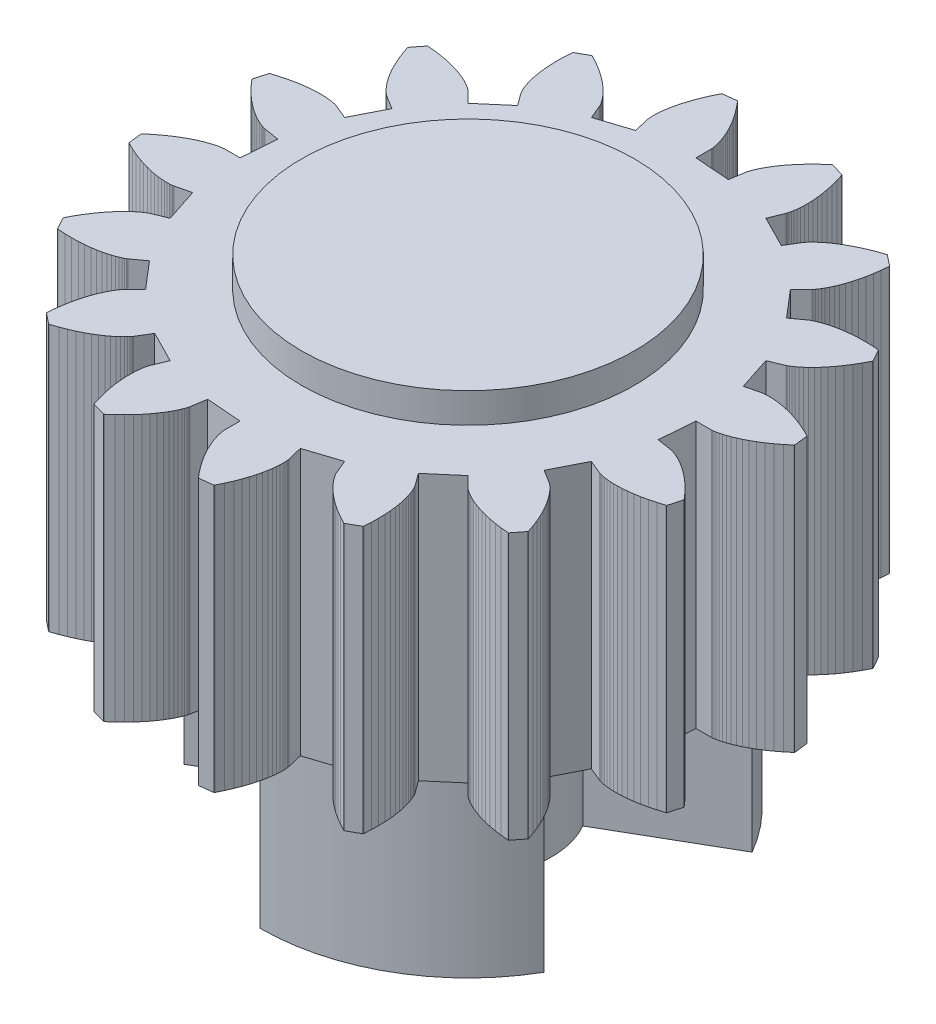
SolidWorks part; units mm, degrees
ref_plane "Front Plane" through (0, 0, 0) normal (0, 0, 1) x (1, 0, 0)
ref_plane "Top Plane" through (0, 0, 0) normal (0, 1, 0) x (1, 0, 0)
ref_plane "Right Plane" through (0, 0, 0) normal (1, 0, 0) x (0, 0, -1)
sketch "Sketch1" plane through (0, 0, 0) normal (0, 1, 0) x (1, 0, 0)
  line L0 (6.85, 0) -> (7.3095, 0)
  line L1 (7.3095, 0) -> (7.322, 0.0006)
  line L2 (7.322, 0.0006) -> (7.3483, 0.0028)
  line L3 (7.3483, 0.0028) -> (7.3883, 0.0079)
  line L4 (7.3883, 0.0079) -> (7.4418, 0.0172)
  line L5 (7.4418, 0.0172) -> (7.5084, 0.0317)
  line L6 (7.5084, 0.0317) -> (7.5878, 0.0526)
  line L7 (7.5878, 0.0526) -> (7.6795, 0.0812)
  line L8 (7.6795, 0.0812) -> (7.7829, 0.1183)
  line L9 (7.7829, 0.1183) -> (7.8975, 0.1653)
  line L10 (7.8975, 0.1653) -> (8.0225, 0.223)
  line L11 (8.0225, 0.223) -> (8.1573, 0.2925)
  line L12 (8.1573, 0.2925) -> (8.3011, 0.3747)
  line L13 (8.3011, 0.3747) -> (8.4528, 0.4705)
  line L14 (8.4528, 0.4705) -> (8.6117, 0.5808)
  line L15 (8.6117, 0.5808) -> (8.7767, 0.7063)
  line L16 (8.7767, 0.7063) -> (8.9467, 0.8478)
  line L17 (8.9467, 0.8478) -> (8.9575, 0.8572)
  line L18 (8.9575, 0.8572) -> (8.9588, 0.8583)
  line L19 (8.9588, 0.8583) -> (8.9589, 0.8586)
  line L20 (8.9589, 0.8586) -> (8.9086, 1.2795)
  line L21 (8.9086, 1.2795) -> (8.9084, 1.2798)
  line L22 (8.9084, 1.2798) -> (8.9068, 1.2806)
  line L23 (8.9068, 1.2806) -> (8.8941, 1.2872)
  line L24 (8.8941, 1.2872) -> (8.6955, 1.3845)
  line L25 (8.6955, 1.3845) -> (8.5056, 1.4676)
  line L26 (8.5056, 1.4676) -> (8.3252, 1.5373)
  line L27 (8.3252, 1.5373) -> (8.1551, 1.5946)
  line L28 (8.1551, 1.5946) -> (7.996, 1.6405)
  line L29 (7.996, 1.6405) -> (7.8486, 1.6762)
  line L30 (7.8486, 1.6762) -> (7.7135, 1.7028)
  line L31 (7.7135, 1.7028) -> (7.5911, 1.7214)
  line L32 (7.5911, 1.7214) -> (7.4818, 1.7331)
  line L33 (7.4818, 1.7331) -> (7.386, 1.7392)
  line L34 (7.386, 1.7392) -> (7.3039, 1.7408)
  line L35 (7.3039, 1.7408) -> (7.2357, 1.7392)
  line L36 (7.2357, 1.7392) -> (7.1816, 1.7356)
  line L37 (7.1816, 1.7356) -> (7.1415, 1.7311)
  line L38 (7.1415, 1.7311) -> (7.1154, 1.7271)
  line L39 (7.1154, 1.7271) -> (7.1031, 1.7247)
  line L40 (7.1031, 1.7247) -> (6.6566, 1.6163)
  line L41 (6.6566, 1.6163) -> (6.3286, 2.6214)
  line L42 (6.3286, 2.6214) -> (6.7531, 2.7972)
  line L43 (6.7531, 2.7972) -> (6.7644, 2.8025)
  line L44 (6.7644, 2.8025) -> (6.7879, 2.8147)
  line L45 (6.7879, 2.8147) -> (6.8229, 2.8347)
  line L46 (6.8229, 2.8347) -> (6.8688, 2.8637)
  line L47 (6.8688, 2.8637) -> (6.9248, 2.9026)
  line L48 (6.9248, 2.9026) -> (6.9901, 2.9524)
  line L49 (6.9901, 2.9524) -> (7.0638, 3.0138)
  line L50 (7.0638, 3.0138) -> (7.1452, 3.0877)
  line L51 (7.1452, 3.0877) -> (7.2331, 3.1749)
  line L52 (7.2331, 3.1749) -> (7.3265, 3.2761)
  line L53 (7.3265, 3.2761) -> (7.4245, 3.3919)
  line L54 (7.4245, 3.3919) -> (7.5258, 3.5228)
  line L55 (7.5258, 3.5228) -> (7.6293, 3.6694)
  line L56 (7.6293, 3.6694) -> (7.7339, 3.8321)
  line L57 (7.7339, 3.8321) -> (7.8383, 4.0112)
  line L58 (7.8383, 4.0112) -> (7.9413, 4.207)
  line L59 (7.9413, 4.207) -> (7.9476, 4.2198)
  line L60 (7.9476, 4.2198) -> (7.9484, 4.2214)
  line L61 (7.9484, 4.2214) -> (7.9484, 4.2217)
  line L62 (7.9484, 4.2217) -> (7.7408, 4.5913)
  line L63 (7.7408, 4.5913) -> (7.7406, 4.5914)
  line L64 (7.7406, 4.5914) -> (7.7388, 4.5916)
  line L65 (7.7388, 4.5916) -> (7.7245, 4.5928)
  line L66 (7.7245, 4.5928) -> (7.5038, 4.6068)
  line L67 (7.5038, 4.6068) -> (7.2965, 4.6108)
  line L68 (7.2965, 4.6108) -> (7.1032, 4.6062)
  line L69 (7.1032, 4.6062) -> (6.9241, 4.594)
  line L70 (6.9241, 4.594) -> (6.7596, 4.5756)
  line L71 (6.7596, 4.5756) -> (6.6097, 4.5522)
  line L72 (6.6097, 4.5522) -> (6.4747, 4.525)
  line L73 (6.4747, 4.525) -> (6.3545, 4.4953)
  line L74 (6.3545, 4.4953) -> (6.249, 4.4644)
  line L75 (6.249, 4.4644) -> (6.1582, 4.4333)
  line L76 (6.1582, 4.4333) -> (6.0817, 4.4034)
  line L77 (6.0817, 4.4034) -> (6.0194, 4.3758)
  line L78 (6.0194, 4.3758) -> (5.9708, 4.3518)
  line L79 (5.9708, 4.3518) -> (5.9354, 4.3323)
  line L80 (5.9354, 4.3323) -> (5.9128, 4.3186)
  line L81 (5.9128, 4.3186) -> (5.9024, 4.3116)
  line L82 (5.9024, 4.3116) -> (5.5314, 4.0406)
  line L83 (5.5314, 4.0406) -> (4.8437, 4.8437)
  line L84 (4.8437, 4.8437) -> (5.1686, 5.1686)
  line L85 (5.1686, 5.1686) -> (5.177, 5.1778)
  line L86 (5.177, 5.1778) -> (5.1941, 5.198)
  line L87 (5.1941, 5.198) -> (5.2187, 5.23)
  line L88 (5.2187, 5.23) -> (5.25, 5.2743)
  line L89 (5.25, 5.2743) -> (5.2869, 5.3317)
  line L90 (5.2869, 5.3317) -> (5.3282, 5.4026)
  line L91 (5.3282, 5.4026) -> (5.3728, 5.4876)
  line L92 (5.3728, 5.4876) -> (5.4197, 5.587)
  line L93 (5.4197, 5.587) -> (5.4675, 5.7012)
  line L94 (5.4675, 5.7012) -> (5.5151, 5.8305)
  line L95 (5.5151, 5.8305) -> (5.5613, 5.9749)
  line L96 (5.5613, 5.9749) -> (5.6048, 6.1347)
  line L97 (5.6048, 6.1347) -> (5.6444, 6.3097)
  line L98 (5.6444, 6.3097) -> (5.6787, 6.5)
  line L99 (5.6787, 6.5) -> (5.7066, 6.7055)
  line L100 (5.7066, 6.7055) -> (5.7268, 6.9258)
  line L101 (5.7268, 6.9258) -> (5.7278, 6.94)
  line L102 (5.7278, 6.94) -> (5.7279, 6.9418)
  line L103 (5.7279, 6.9418) -> (5.7278, 6.9421)
  line L104 (5.7278, 6.9421) -> (5.3946, 7.2041)
  line L105 (5.3946, 7.2041) -> (5.3943, 7.2041)
  line L106 (5.3943, 7.2041) -> (5.3926, 7.2036)
  line L107 (5.3926, 7.2036) -> (5.3789, 7.1993)
  line L108 (5.3789, 7.1993) -> (5.1696, 7.1277)
  line L109 (5.1696, 7.1277) -> (4.9766, 7.0521)
  line L110 (4.9766, 7.0521) -> (4.7998, 6.9738)
  line L111 (4.7998, 6.9738) -> (4.639, 6.894)
  line L112 (4.639, 6.894) -> (4.494, 6.8141)
  line L113 (4.494, 6.8141) -> (4.3645, 6.7351)
  line L114 (4.3645, 6.7351) -> (4.2502, 6.6583)
  line L115 (4.2502, 6.6583) -> (4.1505, 6.5849)
  line L116 (4.1505, 6.5849) -> (4.0649, 6.5159)
  line L117 (4.0649, 6.5159) -> (3.9929, 6.4525)
  line L118 (3.9929, 6.4525) -> (3.9337, 6.3956)
  line L119 (3.9337, 6.3956) -> (3.8866, 6.3463)
  line L120 (3.8866, 6.3463) -> (3.8509, 6.3054)
  line L121 (3.8509, 6.3054) -> (3.8257, 6.2739)
  line L122 (3.8257, 6.2739) -> (3.8101, 6.2526)
  line L123 (3.8101, 6.2526) -> (3.8031, 6.2422)
  line L124 (3.8031, 6.2422) -> (3.564, 5.8498)
  line L125 (3.564, 5.8498) -> (2.6214, 6.3286)
  line L126 (2.6214, 6.3286) -> (2.7972, 6.7531)
  line L127 (2.7972, 6.7531) -> (2.8015, 6.7648)
  line L128 (2.8015, 6.7648) -> (2.8095, 6.79)
  line L129 (2.8095, 6.79) -> (2.8201, 6.829)
  line L130 (2.8201, 6.829) -> (2.832, 6.8819)
  line L131 (2.832, 6.8819) -> (2.8441, 6.949)
  line L132 (2.8441, 6.949) -> (2.8551, 7.0304)
  line L133 (2.8551, 7.0304) -> (2.8638, 7.126)
  line L134 (2.8638, 7.126) -> (2.869, 7.2357)
  line L135 (2.869, 7.2357) -> (2.8695, 7.3596)
  line L136 (2.8695, 7.3596) -> (2.8641, 7.4972)
  line L137 (2.8641, 7.4972) -> (2.8515, 7.6483)
  line L138 (2.8515, 7.6483) -> (2.8305, 7.8126)
  line L139 (2.8305, 7.8126) -> (2.8001, 7.9894)
  line L140 (2.8001, 7.9894) -> (2.759, 8.1784)
  line L141 (2.759, 8.1784) -> (2.7062, 8.3789)
  line L142 (2.7062, 8.3789) -> (2.6405, 8.5901)
  line L143 (2.6405, 8.5901) -> (2.636, 8.6037)
  line L144 (2.636, 8.6037) -> (2.6354, 8.6054)
  line L145 (2.6354, 8.6054) -> (2.6352, 8.6056)
  line L146 (2.6352, 8.6056) -> (2.227, 8.7201)
  line L147 (2.227, 8.7201) -> (2.2268, 8.72)
  line L148 (2.2268, 8.72) -> (2.2254, 8.7189)
  line L149 (2.2254, 8.7189) -> (2.2144, 8.7097)
  line L150 (2.2144, 8.7097) -> (2.0485, 8.5634)
  line L151 (2.0485, 8.5634) -> (1.8991, 8.4197)
  line L152 (1.8991, 8.4197) -> (1.7657, 8.2797)
  line L153 (1.7657, 8.2797) -> (1.6476, 8.1445)
  line L154 (1.6476, 8.1445) -> (1.5443, 8.0152)
  line L155 (1.5443, 8.0152) -> (1.4549, 7.8927)
  line L156 (1.4549, 7.8927) -> (1.3786, 7.778)
  line L157 (1.3786, 7.778) -> (1.3146, 7.672)
  line L158 (1.3146, 7.672) -> (1.262, 7.5755)
  line L159 (1.262, 7.5755) -> (1.2197, 7.4893)
  line L160 (1.2197, 7.4893) -> (1.1868, 7.4141)
  line L161 (1.1868, 7.4141) -> (1.1622, 7.3505)
  line L162 (1.1622, 7.3505) -> (1.1448, 7.2991)
  line L163 (1.1448, 7.2991) -> (1.1336, 7.2604)
  line L164 (1.1336, 7.2604) -> (1.1273, 7.2347)
  line L165 (1.1273, 7.2347) -> (1.1248, 7.2224)
  line L166 (1.1248, 7.2224) -> (1.0541, 6.7684)
  line L167 (1.0541, 6.7684) -> (0, 6.85)
  line L168 (0, 6.85) -> (0, 7.3095)
  line L169 (0, 7.3095) -> (-0.0006, 7.322)
  line L170 (-0.0006, 7.322) -> (-0.0028, 7.3483)
  line L171 (-0.0028, 7.3483) -> (-0.0079, 7.3883)
  line L172 (-0.0079, 7.3883) -> (-0.0172, 7.4418)
  line L173 (-0.0172, 7.4418) -> (-0.0317, 7.5084)
  line L174 (-0.0317, 7.5084) -> (-0.0526, 7.5878)
  line L175 (-0.0526, 7.5878) -> (-0.0812, 7.6795)
  line L176 (-0.0812, 7.6795) -> (-0.1183, 7.7829)
  line L177 (-0.1183, 7.7829) -> (-0.1653, 7.8975)
  line L178 (-0.1653, 7.8975) -> (-0.223, 8.0225)
  line L179 (-0.223, 8.0225) -> (-0.2925, 8.1573)
  line L180 (-0.2925, 8.1573) -> (-0.3747, 8.3011)
  line L181 (-0.3747, 8.3011) -> (-0.4705, 8.4528)
  line L182 (-0.4705, 8.4528) -> (-0.5808, 8.6117)
  line L183 (-0.5808, 8.6117) -> (-0.7063, 8.7767)
  line L184 (-0.7063, 8.7767) -> (-0.8478, 8.9467)
  line L185 (-0.8478, 8.9467) -> (-0.8572, 8.9575)
  line L186 (-0.8572, 8.9575) -> (-0.8583, 8.9588)
  line L187 (-0.8583, 8.9588) -> (-0.8586, 8.9589)
  line L188 (-0.8586, 8.9589) -> (-1.2795, 8.9086)
  line L189 (-1.2795, 8.9086) -> (-1.2798, 8.9084)
  line L190 (-1.2798, 8.9084) -> (-1.2806, 8.9068)
  line L191 (-1.2806, 8.9068) -> (-1.2872, 8.8941)
  line L192 (-1.2872, 8.8941) -> (-1.3845, 8.6955)
  line L193 (-1.3845, 8.6955) -> (-1.4676, 8.5056)
  line L194 (-1.4676, 8.5056) -> (-1.5373, 8.3252)
  line L195 (-1.5373, 8.3252) -> (-1.5946, 8.1551)
  line L196 (-1.5946, 8.1551) -> (-1.6405, 7.996)
  line L197 (-1.6405, 7.996) -> (-1.6762, 7.8486)
  line L198 (-1.6762, 7.8486) -> (-1.7028, 7.7135)
  line L199 (-1.7028, 7.7135) -> (-1.7214, 7.5911)
  line L200 (-1.7214, 7.5911) -> (-1.7331, 7.4818)
  line L201 (-1.7331, 7.4818) -> (-1.7392, 7.386)
  line L202 (-1.7392, 7.386) -> (-1.7408, 7.3039)
  line L203 (-1.7408, 7.3039) -> (-1.7392, 7.2357)
  line L204 (-1.7392, 7.2357) -> (-1.7356, 7.1816)
  line L205 (-1.7356, 7.1816) -> (-1.7311, 7.1415)
  line L206 (-1.7311, 7.1415) -> (-1.7271, 7.1154)
  line L207 (-1.7271, 7.1154) -> (-1.7247, 7.1031)
  line L208 (-1.7247, 7.1031) -> (-1.6163, 6.6566)
  line L209 (-1.6163, 6.6566) -> (-2.6214, 6.3286)
  line L210 (-2.6214, 6.3286) -> (-2.7972, 6.7531)
  line L211 (-2.7972, 6.7531) -> (-2.8025, 6.7644)
  line L212 (-2.8025, 6.7644) -> (-2.8147, 6.7879)
  line L213 (-2.8147, 6.7879) -> (-2.8347, 6.8229)
  line L214 (-2.8347, 6.8229) -> (-2.8637, 6.8688)
  line L215 (-2.8637, 6.8688) -> (-2.9026, 6.9248)
  line L216 (-2.9026, 6.9248) -> (-2.9524, 6.9901)
  line L217 (-2.9524, 6.9901) -> (-3.0138, 7.0638)
  line L218 (-3.0138, 7.0638) -> (-3.0877, 7.1452)
  line L219 (-3.0877, 7.1452) -> (-3.1749, 7.2331)
  line L220 (-3.1749, 7.2331) -> (-3.2761, 7.3265)
  line L221 (-3.2761, 7.3265) -> (-3.3919, 7.4245)
  line L222 (-3.3919, 7.4245) -> (-3.5228, 7.5258)
  line L223 (-3.5228, 7.5258) -> (-3.6694, 7.6293)
  line L224 (-3.6694, 7.6293) -> (-3.8321, 7.7339)
  line L225 (-3.8321, 7.7339) -> (-4.0112, 7.8383)
  line L226 (-4.0112, 7.8383) -> (-4.207, 7.9413)
  line L227 (-4.207, 7.9413) -> (-4.2198, 7.9476)
  line L228 (-4.2198, 7.9476) -> (-4.2214, 7.9484)
  line L229 (-4.2214, 7.9484) -> (-4.2217, 7.9484)
  line L230 (-4.2217, 7.9484) -> (-4.5913, 7.7408)
  line L231 (-4.5913, 7.7408) -> (-4.5914, 7.7406)
  line L232 (-4.5914, 7.7406) -> (-4.5916, 7.7388)
  line L233 (-4.5916, 7.7388) -> (-4.5928, 7.7245)
  line L234 (-4.5928, 7.7245) -> (-4.6068, 7.5038)
  line L235 (-4.6068, 7.5038) -> (-4.6108, 7.2965)
  line L236 (-4.6108, 7.2965) -> (-4.6062, 7.1032)
  line L237 (-4.6062, 7.1032) -> (-4.594, 6.9241)
  line L238 (-4.594, 6.9241) -> (-4.5756, 6.7596)
  line L239 (-4.5756, 6.7596) -> (-4.5522, 6.6097)
  line L240 (-4.5522, 6.6097) -> (-4.525, 6.4747)
  line L241 (-4.525, 6.4747) -> (-4.4953, 6.3545)
  line L242 (-4.4953, 6.3545) -> (-4.4644, 6.249)
  line L243 (-4.4644, 6.249) -> (-4.4333, 6.1582)
  line L244 (-4.4333, 6.1582) -> (-4.4034, 6.0817)
  line L245 (-4.4034, 6.0817) -> (-4.3758, 6.0194)
  line L246 (-4.3758, 6.0194) -> (-4.3518, 5.9708)
  line L247 (-4.3518, 5.9708) -> (-4.3323, 5.9354)
  line L248 (-4.3323, 5.9354) -> (-4.3186, 5.9128)
  line L249 (-4.3186, 5.9128) -> (-4.3116, 5.9024)
  line L250 (-4.3116, 5.9024) -> (-4.0406, 5.5314)
  line L251 (-4.0406, 5.5314) -> (-4.8437, 4.8437)
  line L252 (-4.8437, 4.8437) -> (-5.1686, 5.1686)
  line L253 (-5.1686, 5.1686) -> (-5.1778, 5.177)
  line L254 (-5.1778, 5.177) -> (-5.198, 5.1941)
  line L255 (-5.198, 5.1941) -> (-5.23, 5.2187)
  line L256 (-5.23, 5.2187) -> (-5.2743, 5.25)
  line L257 (-5.2743, 5.25) -> (-5.3317, 5.2869)
  line L258 (-5.3317, 5.2869) -> (-5.4026, 5.3282)
  line L259 (-5.4026, 5.3282) -> (-5.4876, 5.3728)
  line L260 (-5.4876, 5.3728) -> (-5.587, 5.4197)
  line L261 (-5.587, 5.4197) -> (-5.7012, 5.4675)
  line L262 (-5.7012, 5.4675) -> (-5.8305, 5.5151)
  line L263 (-5.8305, 5.5151) -> (-5.9749, 5.5613)
  line L264 (-5.9749, 5.5613) -> (-6.1347, 5.6048)
  line L265 (-6.1347, 5.6048) -> (-6.3097, 5.6444)
  line L266 (-6.3097, 5.6444) -> (-6.5, 5.6787)
  line L267 (-6.5, 5.6787) -> (-6.7055, 5.7066)
  line L268 (-6.7055, 5.7066) -> (-6.9258, 5.7268)
  line L269 (-6.9258, 5.7268) -> (-6.94, 5.7278)
  line L270 (-6.94, 5.7278) -> (-6.9418, 5.7279)
  line L271 (-6.9418, 5.7279) -> (-6.9421, 5.7278)
  line L272 (-6.9421, 5.7278) -> (-7.2041, 5.3946)
  line L273 (-7.2041, 5.3946) -> (-7.2041, 5.3943)
  line L274 (-7.2041, 5.3943) -> (-7.2036, 5.3926)
  line L275 (-7.2036, 5.3926) -> (-7.1993, 5.3789)
  line L276 (-7.1993, 5.3789) -> (-7.1277, 5.1696)
  line L277 (-7.1277, 5.1696) -> (-7.0521, 4.9766)
  line L278 (-7.0521, 4.9766) -> (-6.9738, 4.7998)
  line L279 (-6.9738, 4.7998) -> (-6.894, 4.639)
  line L280 (-6.894, 4.639) -> (-6.8141, 4.494)
  line L281 (-6.8141, 4.494) -> (-6.7351, 4.3645)
  line L282 (-6.7351, 4.3645) -> (-6.6583, 4.2502)
  line L283 (-6.6583, 4.2502) -> (-6.5849, 4.1505)
  line L284 (-6.5849, 4.1505) -> (-6.5159, 4.0649)
  line L285 (-6.5159, 4.0649) -> (-6.4525, 3.9929)
  line L286 (-6.4525, 3.9929) -> (-6.3956, 3.9337)
  line L287 (-6.3956, 3.9337) -> (-6.3463, 3.8866)
  line L288 (-6.3463, 3.8866) -> (-6.3054, 3.8509)
  line L289 (-6.3054, 3.8509) -> (-6.2739, 3.8257)
  line L290 (-6.2739, 3.8257) -> (-6.2526, 3.8101)
  line L291 (-6.2526, 3.8101) -> (-6.2422, 3.8031)
  line L292 (-6.2422, 3.8031) -> (-5.8498, 3.564)
  line L293 (-5.8498, 3.564) -> (-6.3286, 2.6214)
  line L294 (-6.3286, 2.6214) -> (-6.7531, 2.7972)
  line L295 (-6.7531, 2.7972) -> (-6.7648, 2.8015)
  line L296 (-6.7648, 2.8015) -> (-6.79, 2.8095)
  line L297 (-6.79, 2.8095) -> (-6.829, 2.8201)
  line L298 (-6.829, 2.8201) -> (-6.8819, 2.832)
  line L299 (-6.8819, 2.832) -> (-6.949, 2.8441)
  line L300 (-6.949, 2.8441) -> (-7.0304, 2.8551)
  line L301 (-7.0304, 2.8551) -> (-7.126, 2.8638)
  line L302 (-7.126, 2.8638) -> (-7.2357, 2.869)
  line L303 (-7.2357, 2.869) -> (-7.3596, 2.8695)
  line L304 (-7.3596, 2.8695) -> (-7.4972, 2.8641)
  line L305 (-7.4972, 2.8641) -> (-7.6483, 2.8515)
  line L306 (-7.6483, 2.8515) -> (-7.8126, 2.8305)
  line L307 (-7.8126, 2.8305) -> (-7.9894, 2.8001)
  line L308 (-7.9894, 2.8001) -> (-8.1784, 2.759)
  line L309 (-8.1784, 2.759) -> (-8.3789, 2.7062)
  line L310 (-8.3789, 2.7062) -> (-8.5901, 2.6405)
  line L311 (-8.5901, 2.6405) -> (-8.6037, 2.636)
  line L312 (-8.6037, 2.636) -> (-8.6054, 2.6354)
  line L313 (-8.6054, 2.6354) -> (-8.6056, 2.6352)
  line L314 (-8.6056, 2.6352) -> (-8.7201, 2.227)
  line L315 (-8.7201, 2.227) -> (-8.72, 2.2268)
  line L316 (-8.72, 2.2268) -> (-8.7189, 2.2254)
  line L317 (-8.7189, 2.2254) -> (-8.7097, 2.2144)
  line L318 (-8.7097, 2.2144) -> (-8.5634, 2.0485)
  line L319 (-8.5634, 2.0485) -> (-8.4197, 1.8991)
  line L320 (-8.4197, 1.8991) -> (-8.2797, 1.7657)
  line L321 (-8.2797, 1.7657) -> (-8.1445, 1.6476)
  line L322 (-8.1445, 1.6476) -> (-8.0152, 1.5443)
  line L323 (-8.0152, 1.5443) -> (-7.8927, 1.4549)
  line L324 (-7.8927, 1.4549) -> (-7.778, 1.3786)
  line L325 (-7.778, 1.3786) -> (-7.672, 1.3146)
  line L326 (-7.672, 1.3146) -> (-7.5755, 1.262)
  line L327 (-7.5755, 1.262) -> (-7.4893, 1.2197)
  line L328 (-7.4893, 1.2197) -> (-7.4141, 1.1868)
  line L329 (-7.4141, 1.1868) -> (-7.3505, 1.1622)
  line L330 (-7.3505, 1.1622) -> (-7.2991, 1.1448)
  line L331 (-7.2991, 1.1448) -> (-7.2604, 1.1336)
  line L332 (-7.2604, 1.1336) -> (-7.2347, 1.1273)
  line L333 (-7.2347, 1.1273) -> (-7.2224, 1.1248)
  line L334 (-7.2224, 1.1248) -> (-6.7684, 1.0541)
  line L335 (-6.7684, 1.0541) -> (-6.85, 0)
  line L336 (-6.85, 0) -> (-7.3095, 0)
  line L337 (-7.3095, 0) -> (-7.322, -0.0006)
  line L338 (-7.322, -0.0006) -> (-7.3483, -0.0028)
  line L339 (-7.3483, -0.0028) -> (-7.3883, -0.0079)
  line L340 (-7.3883, -0.0079) -> (-7.4418, -0.0172)
  line L341 (-7.4418, -0.0172) -> (-7.5084, -0.0317)
  line L342 (-7.5084, -0.0317) -> (-7.5878, -0.0526)
  line L343 (-7.5878, -0.0526) -> (-7.6795, -0.0812)
  line L344 (-7.6795, -0.0812) -> (-7.7829, -0.1183)
  line L345 (-7.7829, -0.1183) -> (-7.8975, -0.1653)
  line L346 (-7.8975, -0.1653) -> (-8.0225, -0.223)
  line L347 (-8.0225, -0.223) -> (-8.1573, -0.2925)
  line L348 (-8.1573, -0.2925) -> (-8.3011, -0.3747)
  line L349 (-8.3011, -0.3747) -> (-8.4528, -0.4705)
  line L350 (-8.4528, -0.4705) -> (-8.6117, -0.5808)
  line L351 (-8.6117, -0.5808) -> (-8.7767, -0.7063)
  line L352 (-8.7767, -0.7063) -> (-8.9467, -0.8478)
  line L353 (-8.9467, -0.8478) -> (-8.9575, -0.8572)
  line L354 (-8.9575, -0.8572) -> (-8.9588, -0.8583)
  line L355 (-8.9588, -0.8583) -> (-8.9589, -0.8586)
  line L356 (-8.9589, -0.8586) -> (-8.9086, -1.2795)
  line L357 (-8.9086, -1.2795) -> (-8.9084, -1.2798)
  line L358 (-8.9084, -1.2798) -> (-8.9068, -1.2806)
  line L359 (-8.9068, -1.2806) -> (-8.8941, -1.2872)
  line L360 (-8.8941, -1.2872) -> (-8.6955, -1.3845)
  line L361 (-8.6955, -1.3845) -> (-8.5056, -1.4676)
  line L362 (-8.5056, -1.4676) -> (-8.3252, -1.5373)
  line L363 (-8.3252, -1.5373) -> (-8.1551, -1.5946)
  line L364 (-8.1551, -1.5946) -> (-7.996, -1.6405)
  line L365 (-7.996, -1.6405) -> (-7.8486, -1.6762)
  line L366 (-7.8486, -1.6762) -> (-7.7135, -1.7028)
  line L367 (-7.7135, -1.7028) -> (-7.5911, -1.7214)
  line L368 (-7.5911, -1.7214) -> (-7.4818, -1.7331)
  line L369 (-7.4818, -1.7331) -> (-7.386, -1.7392)
  line L370 (-7.386, -1.7392) -> (-7.3039, -1.7408)
  line L371 (-7.3039, -1.7408) -> (-7.2357, -1.7392)
  line L372 (-7.2357, -1.7392) -> (-7.1816, -1.7356)
  line L373 (-7.1816, -1.7356) -> (-7.1415, -1.7311)
  line L374 (-7.1415, -1.7311) -> (-7.1154, -1.7271)
  line L375 (-7.1154, -1.7271) -> (-7.1031, -1.7247)
  line L376 (-7.1031, -1.7247) -> (-6.6566, -1.6163)
  line L377 (-6.6566, -1.6163) -> (-6.3286, -2.6214)
  line L378 (-6.3286, -2.6214) -> (-6.7531, -2.7972)
  line L379 (-6.7531, -2.7972) -> (-6.7644, -2.8025)
  line L380 (-6.7644, -2.8025) -> (-6.7879, -2.8147)
  line L381 (-6.7879, -2.8147) -> (-6.8229, -2.8347)
  line L382 (-6.8229, -2.8347) -> (-6.8688, -2.8637)
  line L383 (-6.8688, -2.8637) -> (-6.9248, -2.9026)
  line L384 (-6.9248, -2.9026) -> (-6.9901, -2.9524)
  line L385 (-6.9901, -2.9524) -> (-7.0638, -3.0138)
  line L386 (-7.0638, -3.0138) -> (-7.1452, -3.0877)
  line L387 (-7.1452, -3.0877) -> (-7.2331, -3.1749)
  line L388 (-7.2331, -3.1749) -> (-7.3265, -3.2761)
  line L389 (-7.3265, -3.2761) -> (-7.4245, -3.3919)
  line L390 (-7.4245, -3.3919) -> (-7.5258, -3.5228)
  line L391 (-7.5258, -3.5228) -> (-7.6293, -3.6694)
  line L392 (-7.6293, -3.6694) -> (-7.7339, -3.8321)
  line L393 (-7.7339, -3.8321) -> (-7.8383, -4.0112)
  line L394 (-7.8383, -4.0112) -> (-7.9413, -4.207)
  line L395 (-7.9413, -4.207) -> (-7.9476, -4.2198)
  line L396 (-7.9476, -4.2198) -> (-7.9484, -4.2214)
  line L397 (-7.9484, -4.2214) -> (-7.9484, -4.2217)
  line L398 (-7.9484, -4.2217) -> (-7.7408, -4.5913)
  line L399 (-7.7408, -4.5913) -> (-7.7406, -4.5914)
  line L400 (-7.7406, -4.5914) -> (-7.7388, -4.5916)
  line L401 (-7.7388, -4.5916) -> (-7.7245, -4.5928)
  line L402 (-7.7245, -4.5928) -> (-7.5038, -4.6068)
  line L403 (-7.5038, -4.6068) -> (-7.2965, -4.6108)
  line L404 (-7.2965, -4.6108) -> (-7.1032, -4.6062)
  line L405 (-7.1032, -4.6062) -> (-6.9241, -4.594)
  line L406 (-6.9241, -4.594) -> (-6.7596, -4.5756)
  line L407 (-6.7596, -4.5756) -> (-6.6097, -4.5522)
  line L408 (-6.6097, -4.5522) -> (-6.4747, -4.525)
  line L409 (-6.4747, -4.525) -> (-6.3545, -4.4953)
  line L410 (-6.3545, -4.4953) -> (-6.249, -4.4644)
  line L411 (-6.249, -4.4644) -> (-6.1582, -4.4333)
  line L412 (-6.1582, -4.4333) -> (-6.0817, -4.4034)
  line L413 (-6.0817, -4.4034) -> (-6.0194, -4.3758)
  line L414 (-6.0194, -4.3758) -> (-5.9708, -4.3518)
  line L415 (-5.9708, -4.3518) -> (-5.9354, -4.3323)
  line L416 (-5.9354, -4.3323) -> (-5.9128, -4.3186)
  line L417 (-5.9128, -4.3186) -> (-5.9024, -4.3116)
  line L418 (-5.9024, -4.3116) -> (-5.5314, -4.0406)
  line L419 (-5.5314, -4.0406) -> (-4.8437, -4.8437)
  line L420 (-4.8437, -4.8437) -> (-5.1686, -5.1686)
  line L421 (-5.1686, -5.1686) -> (-5.177, -5.1778)
  line L422 (-5.177, -5.1778) -> (-5.1941, -5.198)
  line L423 (-5.1941, -5.198) -> (-5.2187, -5.23)
  line L424 (-5.2187, -5.23) -> (-5.25, -5.2743)
  line L425 (-5.25, -5.2743) -> (-5.2869, -5.3317)
  line L426 (-5.2869, -5.3317) -> (-5.3282, -5.4026)
  line L427 (-5.3282, -5.4026) -> (-5.3728, -5.4876)
  line L428 (-5.3728, -5.4876) -> (-5.4197, -5.587)
  line L429 (-5.4197, -5.587) -> (-5.4675, -5.7012)
  line L430 (-5.4675, -5.7012) -> (-5.5151, -5.8305)
  line L431 (-5.5151, -5.8305) -> (-5.5613, -5.9749)
  line L432 (-5.5613, -5.9749) -> (-5.6048, -6.1347)
  line L433 (-5.6048, -6.1347) -> (-5.6444, -6.3097)
  line L434 (-5.6444, -6.3097) -> (-5.6787, -6.5)
  line L435 (-5.6787, -6.5) -> (-5.7066, -6.7055)
  line L436 (-5.7066, -6.7055) -> (-5.7268, -6.9258)
  line L437 (-5.7268, -6.9258) -> (-5.7278, -6.94)
  line L438 (-5.7278, -6.94) -> (-5.7279, -6.9418)
  line L439 (-5.7279, -6.9418) -> (-5.7278, -6.9421)
  line L440 (-5.7278, -6.9421) -> (-5.3946, -7.2041)
  line L441 (-5.3946, -7.2041) -> (-5.3943, -7.2041)
  line L442 (-5.3943, -7.2041) -> (-5.3926, -7.2036)
  line L443 (-5.3926, -7.2036) -> (-5.3789, -7.1993)
  line L444 (-5.3789, -7.1993) -> (-5.1696, -7.1277)
  line L445 (-5.1696, -7.1277) -> (-4.9766, -7.0521)
  line L446 (-4.9766, -7.0521) -> (-4.7998, -6.9738)
  line L447 (-4.7998, -6.9738) -> (-4.639, -6.894)
  line L448 (-4.639, -6.894) -> (-4.494, -6.8141)
  line L449 (-4.494, -6.8141) -> (-4.3645, -6.7351)
  line L450 (-4.3645, -6.7351) -> (-4.2502, -6.6583)
  line L451 (-4.2502, -6.6583) -> (-4.1505, -6.5849)
  line L452 (-4.1505, -6.5849) -> (-4.0649, -6.5159)
  line L453 (-4.0649, -6.5159) -> (-3.9929, -6.4525)
  line L454 (-3.9929, -6.4525) -> (-3.9337, -6.3956)
  line L455 (-3.9337, -6.3956) -> (-3.8866, -6.3463)
  line L456 (-3.8866, -6.3463) -> (-3.8509, -6.3054)
  line L457 (-3.8509, -6.3054) -> (-3.8257, -6.2739)
  line L458 (-3.8257, -6.2739) -> (-3.8101, -6.2526)
  line L459 (-3.8101, -6.2526) -> (-3.8031, -6.2422)
  line L460 (-3.8031, -6.2422) -> (-3.564, -5.8498)
  line L461 (-3.564, -5.8498) -> (-2.6214, -6.3286)
  line L462 (-2.6214, -6.3286) -> (-2.7972, -6.7531)
  line L463 (-2.7972, -6.7531) -> (-2.8015, -6.7648)
  line L464 (-2.8015, -6.7648) -> (-2.8095, -6.79)
  line L465 (-2.8095, -6.79) -> (-2.8201, -6.829)
  line L466 (-2.8201, -6.829) -> (-2.832, -6.8819)
  line L467 (-2.832, -6.8819) -> (-2.8441, -6.949)
  line L468 (-2.8441, -6.949) -> (-2.8551, -7.0304)
  line L469 (-2.8551, -7.0304) -> (-2.8638, -7.126)
  line L470 (-2.8638, -7.126) -> (-2.869, -7.2357)
  line L471 (-2.869, -7.2357) -> (-2.8695, -7.3596)
  line L472 (-2.8695, -7.3596) -> (-2.8641, -7.4972)
  line L473 (-2.8641, -7.4972) -> (-2.8515, -7.6483)
  line L474 (-2.8515, -7.6483) -> (-2.8305, -7.8126)
  line L475 (-2.8305, -7.8126) -> (-2.8001, -7.9894)
  line L476 (-2.8001, -7.9894) -> (-2.759, -8.1784)
  line L477 (-2.759, -8.1784) -> (-2.7062, -8.3789)
  line L478 (-2.7062, -8.3789) -> (-2.6405, -8.5901)
  line L479 (-2.6405, -8.5901) -> (-2.636, -8.6037)
  line L480 (-2.636, -8.6037) -> (-2.6354, -8.6054)
  line L481 (-2.6354, -8.6054) -> (-2.6352, -8.6056)
  line L482 (-2.6352, -8.6056) -> (-2.227, -8.7201)
  line L483 (-2.227, -8.7201) -> (-2.2268, -8.72)
  line L484 (-2.2268, -8.72) -> (-2.2254, -8.7189)
  line L485 (-2.2254, -8.7189) -> (-2.2144, -8.7097)
  line L486 (-2.2144, -8.7097) -> (-2.0485, -8.5634)
  line L487 (-2.0485, -8.5634) -> (-1.8991, -8.4197)
  line L488 (-1.8991, -8.4197) -> (-1.7657, -8.2797)
  line L489 (-1.7657, -8.2797) -> (-1.6476, -8.1445)
  line L490 (-1.6476, -8.1445) -> (-1.5443, -8.0152)
  line L491 (-1.5443, -8.0152) -> (-1.4549, -7.8927)
  line L492 (-1.4549, -7.8927) -> (-1.3786, -7.778)
  line L493 (-1.3786, -7.778) -> (-1.3146, -7.672)
  line L494 (-1.3146, -7.672) -> (-1.262, -7.5755)
  line L495 (-1.262, -7.5755) -> (-1.2197, -7.4893)
  line L496 (-1.2197, -7.4893) -> (-1.1868, -7.4141)
  line L497 (-1.1868, -7.4141) -> (-1.1622, -7.3505)
  line L498 (-1.1622, -7.3505) -> (-1.1448, -7.2991)
  line L499 (-1.1448, -7.2991) -> (-1.1336, -7.2604)
  line L500 (-1.1336, -7.2604) -> (-1.1273, -7.2347)
  line L501 (-1.1273, -7.2347) -> (-1.1248, -7.2224)
  line L502 (-1.1248, -7.2224) -> (-1.0541, -6.7684)
  line L503 (-1.0541, -6.7684) -> (0, -6.85)
  line L504 (0, -6.85) -> (0, -7.3095)
  line L505 (0, -7.3095) -> (0.0006, -7.322)
  line L506 (0.0006, -7.322) -> (0.0028, -7.3483)
  line L507 (0.0028, -7.3483) -> (0.0079, -7.3883)
  line L508 (0.0079, -7.3883) -> (0.0172, -7.4418)
  line L509 (0.0172, -7.4418) -> (0.0317, -7.5084)
  line L510 (0.0317, -7.5084) -> (0.0526, -7.5878)
  line L511 (0.0526, -7.5878) -> (0.0812, -7.6795)
  line L512 (0.0812, -7.6795) -> (0.1183, -7.7829)
  line L513 (0.1183, -7.7829) -> (0.1653, -7.8975)
  line L514 (0.1653, -7.8975) -> (0.223, -8.0225)
  line L515 (0.223, -8.0225) -> (0.2925, -8.1573)
  line L516 (0.2925, -8.1573) -> (0.3747, -8.3011)
  line L517 (0.3747, -8.3011) -> (0.4705, -8.4528)
  line L518 (0.4705, -8.4528) -> (0.5808, -8.6117)
  line L519 (0.5808, -8.6117) -> (0.7063, -8.7767)
  line L520 (0.7063, -8.7767) -> (0.8478, -8.9467)
  line L521 (0.8478, -8.9467) -> (0.8572, -8.9575)
  line L522 (0.8572, -8.9575) -> (0.8583, -8.9588)
  line L523 (0.8583, -8.9588) -> (0.8586, -8.9589)
  line L524 (0.8586, -8.9589) -> (1.2795, -8.9086)
  line L525 (1.2795, -8.9086) -> (1.2798, -8.9084)
  line L526 (1.2798, -8.9084) -> (1.2806, -8.9068)
  line L527 (1.2806, -8.9068) -> (1.2872, -8.8941)
  line L528 (1.2872, -8.8941) -> (1.3845, -8.6955)
  line L529 (1.3845, -8.6955) -> (1.4676, -8.5056)
  line L530 (1.4676, -8.5056) -> (1.5373, -8.3252)
  line L531 (1.5373, -8.3252) -> (1.5946, -8.1551)
  line L532 (1.5946, -8.1551) -> (1.6405, -7.996)
  line L533 (1.6405, -7.996) -> (1.6762, -7.8486)
  line L534 (1.6762, -7.8486) -> (1.7028, -7.7135)
  line L535 (1.7028, -7.7135) -> (1.7214, -7.5911)
  line L536 (1.7214, -7.5911) -> (1.7331, -7.4818)
  line L537 (1.7331, -7.4818) -> (1.7392, -7.386)
  line L538 (1.7392, -7.386) -> (1.7408, -7.3039)
  line L539 (1.7408, -7.3039) -> (1.7392, -7.2357)
  line L540 (1.7392, -7.2357) -> (1.7356, -7.1816)
  line L541 (1.7356, -7.1816) -> (1.7311, -7.1415)
  line L542 (1.7311, -7.1415) -> (1.7271, -7.1154)
  line L543 (1.7271, -7.1154) -> (1.7247, -7.1031)
  line L544 (1.7247, -7.1031) -> (1.6163, -6.6566)
  line L545 (1.6163, -6.6566) -> (2.6214, -6.3286)
  line L546 (2.6214, -6.3286) -> (2.7972, -6.7531)
  line L547 (2.7972, -6.7531) -> (2.8025, -6.7644)
  line L548 (2.8025, -6.7644) -> (2.8147, -6.7879)
  line L549 (2.8147, -6.7879) -> (2.8347, -6.8229)
  line L550 (2.8347, -6.8229) -> (2.8637, -6.8688)
  line L551 (2.8637, -6.8688) -> (2.9026, -6.9248)
  line L552 (2.9026, -6.9248) -> (2.9524, -6.9901)
  line L553 (2.9524, -6.9901) -> (3.0138, -7.0638)
  line L554 (3.0138, -7.0638) -> (3.0877, -7.1452)
  line L555 (3.0877, -7.1452) -> (3.1749, -7.2331)
  line L556 (3.1749, -7.2331) -> (3.2761, -7.3265)
  line L557 (3.2761, -7.3265) -> (3.3919, -7.4245)
  line L558 (3.3919, -7.4245) -> (3.5228, -7.5258)
  line L559 (3.5228, -7.5258) -> (3.6694, -7.6293)
  line L560 (3.6694, -7.6293) -> (3.8321, -7.7339)
  line L561 (3.8321, -7.7339) -> (4.0112, -7.8383)
  line L562 (4.0112, -7.8383) -> (4.207, -7.9413)
  line L563 (4.207, -7.9413) -> (4.2198, -7.9476)
  line L564 (4.2198, -7.9476) -> (4.2214, -7.9484)
  line L565 (4.2214, -7.9484) -> (4.2217, -7.9484)
  line L566 (4.2217, -7.9484) -> (4.5913, -7.7408)
  line L567 (4.5913, -7.7408) -> (4.5914, -7.7406)
  line L568 (4.5914, -7.7406) -> (4.5916, -7.7388)
  line L569 (4.5916, -7.7388) -> (4.5928, -7.7245)
  line L570 (4.5928, -7.7245) -> (4.6068, -7.5038)
  line L571 (4.6068, -7.5038) -> (4.6108, -7.2965)
  line L572 (4.6108, -7.2965) -> (4.6062, -7.1032)
  line L573 (4.6062, -7.1032) -> (4.594, -6.9241)
  line L574 (4.594, -6.9241) -> (4.5756, -6.7596)
  line L575 (4.5756, -6.7596) -> (4.5522, -6.6097)
  line L576 (4.5522, -6.6097) -> (4.525, -6.4747)
  line L577 (4.525, -6.4747) -> (4.4953, -6.3545)
  line L578 (4.4953, -6.3545) -> (4.4644, -6.249)
  line L579 (4.4644, -6.249) -> (4.4333, -6.1582)
  line L580 (4.4333, -6.1582) -> (4.4034, -6.0817)
  line L581 (4.4034, -6.0817) -> (4.3758, -6.0194)
  line L582 (4.3758, -6.0194) -> (4.3518, -5.9708)
  line L583 (4.3518, -5.9708) -> (4.3323, -5.9354)
  line L584 (4.3323, -5.9354) -> (4.3186, -5.9128)
  line L585 (4.3186, -5.9128) -> (4.3116, -5.9024)
  line L586 (4.3116, -5.9024) -> (4.0406, -5.5314)
  line L587 (4.0406, -5.5314) -> (4.8437, -4.8437)
  line L588 (4.8437, -4.8437) -> (5.1686, -5.1686)
  line L589 (5.1686, -5.1686) -> (5.1778, -5.177)
  line L590 (5.1778, -5.177) -> (5.198, -5.1941)
  line L591 (5.198, -5.1941) -> (5.23, -5.2187)
  line L592 (5.23, -5.2187) -> (5.2743, -5.25)
  line L593 (5.2743, -5.25) -> (5.3317, -5.2869)
  line L594 (5.3317, -5.2869) -> (5.4026, -5.3282)
  line L595 (5.4026, -5.3282) -> (5.4876, -5.3728)
  line L596 (5.4876, -5.3728) -> (5.587, -5.4197)
  line L597 (5.587, -5.4197) -> (5.7012, -5.4675)
  line L598 (5.7012, -5.4675) -> (5.8305, -5.5151)
  line L599 (5.8305, -5.5151) -> (5.9749, -5.5613)
  line L600 (5.9749, -5.5613) -> (6.1347, -5.6048)
  line L601 (6.1347, -5.6048) -> (6.3097, -5.6444)
  line L602 (6.3097, -5.6444) -> (6.5, -5.6787)
  line L603 (6.5, -5.6787) -> (6.7055, -5.7066)
  line L604 (6.7055, -5.7066) -> (6.9258, -5.7268)
  line L605 (6.9258, -5.7268) -> (6.94, -5.7278)
  line L606 (6.94, -5.7278) -> (6.9418, -5.7279)
  line L607 (6.9418, -5.7279) -> (6.9421, -5.7278)
  line L608 (6.9421, -5.7278) -> (7.2041, -5.3946)
  line L609 (7.2041, -5.3946) -> (7.2041, -5.3943)
  line L610 (7.2041, -5.3943) -> (7.2036, -5.3926)
  line L611 (7.2036, -5.3926) -> (7.1993, -5.3789)
  line L612 (7.1993, -5.3789) -> (7.1277, -5.1696)
  line L613 (7.1277, -5.1696) -> (7.0521, -4.9766)
  line L614 (7.0521, -4.9766) -> (6.9738, -4.7998)
  line L615 (6.9738, -4.7998) -> (6.894, -4.639)
  line L616 (6.894, -4.639) -> (6.8141, -4.494)
  line L617 (6.8141, -4.494) -> (6.7351, -4.3645)
  line L618 (6.7351, -4.3645) -> (6.6583, -4.2502)
  line L619 (6.6583, -4.2502) -> (6.5849, -4.1505)
  line L620 (6.5849, -4.1505) -> (6.5159, -4.0649)
  line L621 (6.5159, -4.0649) -> (6.4525, -3.9929)
  line L622 (6.4525, -3.9929) -> (6.3956, -3.9337)
  line L623 (6.3956, -3.9337) -> (6.3463, -3.8866)
  line L624 (6.3463, -3.8866) -> (6.3054, -3.8509)
  line L625 (6.3054, -3.8509) -> (6.2739, -3.8257)
  line L626 (6.2739, -3.8257) -> (6.2526, -3.8101)
  line L627 (6.2526, -3.8101) -> (6.2422, -3.8031)
  line L628 (6.2422, -3.8031) -> (5.8498, -3.564)
  line L629 (5.8498, -3.564) -> (6.3286, -2.6214)
  line L630 (6.3286, -2.6214) -> (6.7531, -2.7972)
  line L631 (6.7531, -2.7972) -> (6.7648, -2.8015)
  line L632 (6.7648, -2.8015) -> (6.79, -2.8095)
  line L633 (6.79, -2.8095) -> (6.829, -2.8201)
  line L634 (6.829, -2.8201) -> (6.8819, -2.832)
  line L635 (6.8819, -2.832) -> (6.949, -2.8441)
  line L636 (6.949, -2.8441) -> (7.0304, -2.8551)
  line L637 (7.0304, -2.8551) -> (7.126, -2.8638)
  line L638 (7.126, -2.8638) -> (7.2357, -2.869)
  line L639 (7.2357, -2.869) -> (7.3596, -2.8695)
  line L640 (7.3596, -2.8695) -> (7.4972, -2.8641)
  line L641 (7.4972, -2.8641) -> (7.6483, -2.8515)
  line L642 (7.6483, -2.8515) -> (7.8126, -2.8305)
  line L643 (7.8126, -2.8305) -> (7.9894, -2.8001)
  line L644 (7.9894, -2.8001) -> (8.1784, -2.759)
  line L645 (8.1784, -2.759) -> (8.3789, -2.7062)
  line L646 (8.3789, -2.7062) -> (8.5901, -2.6405)
  line L647 (8.5901, -2.6405) -> (8.6037, -2.636)
  line L648 (8.6037, -2.636) -> (8.6054, -2.6354)
  line L649 (8.6054, -2.6354) -> (8.6056, -2.6352)
  line L650 (8.6056, -2.6352) -> (8.7201, -2.227)
  line L651 (8.7201, -2.227) -> (8.72, -2.2268)
  line L652 (8.72, -2.2268) -> (8.7189, -2.2254)
  line L653 (8.7189, -2.2254) -> (8.7097, -2.2144)
  line L654 (8.7097, -2.2144) -> (8.5634, -2.0485)
  line L655 (8.5634, -2.0485) -> (8.4197, -1.8991)
  line L656 (8.4197, -1.8991) -> (8.2797, -1.7657)
  line L657 (8.2797, -1.7657) -> (8.1445, -1.6476)
  line L658 (8.1445, -1.6476) -> (8.0152, -1.5443)
  line L659 (8.0152, -1.5443) -> (7.8927, -1.4549)
  line L660 (7.8927, -1.4549) -> (7.778, -1.3786)
  line L661 (7.778, -1.3786) -> (7.672, -1.3146)
  line L662 (7.672, -1.3146) -> (7.5755, -1.262)
  line L663 (7.5755, -1.262) -> (7.4893, -1.2197)
  line L664 (7.4893, -1.2197) -> (7.4141, -1.1868)
  line L665 (7.4141, -1.1868) -> (7.3505, -1.1622)
  line L666 (7.3505, -1.1622) -> (7.2991, -1.1448)
  line L667 (7.2991, -1.1448) -> (7.2604, -1.1336)
  line L668 (7.2604, -1.1336) -> (7.2347, -1.1273)
  line L669 (7.2347, -1.1273) -> (7.2224, -1.1248)
  line L670 (7.2224, -1.1248) -> (6.7684, -1.0541)
  line L671 (6.7684, -1.0541) -> (6.85, 0)
  circle A0 centre (0, 0) radius 8 construction
  dimension "D1" = 16
extrude "Boss-Extrude1" add sketch "Sketch1" along normal blind 8
sketch "Sketch2" plane through (0, 8, 0) normal (0, 1, 0) x (1, 0, 0)
  circle A0 centre (0, 0) radius 2.525
  dimension "D1" = 5.05
extrude "Cut-Extrude1" cut sketch "Sketch2" against normal through all both and the other way through all
sketch "Sketch3" plane through (0, 0, 0) normal (0, -1, 0) x (1, 0, 0)
  circle A0 centre (0, 0) radius 6.25
  circle A1 centre (0, 0) radius 2.525 construction
  circle A2 centre (0, 0) radius 2.525
  dimension "D1" = 12.5
extrude "Boss-Extrude2" add sketch "Sketch3" along normal blind 5.5 contours A0 A2 region at (-6.0732, 0, 0)
sketch "Sketch4" plane through (0, 8, 0) normal (0, 1, 0) x (1, 0, 0)
  circle A0 centre (0, 0) radius 2.5
  circle A1 centre (0, 0) radius 5
  dimension "D1" = 5
  dimension "D2" = 10
extrude "Boss-Extrude3" add sketch "Sketch4" along normal blind 0.9
sketch "Sketch5" plane through (0, -5.5, 0) normal (0, -1, 0) x (1, 0, 0)
  line L0 (10.744, -6.2031) -> (-10.3342, 5.9665)
  line L1 (0, 12.4061) -> (0, -11.9329)
  line L2 (-10.744, -6.2031) -> (10.3342, 5.9665)
  circle A0 centre (0, 0) radius 10.3831
  point P11 (0, 0)
  circle M1 centre (0, 0) radius 2.525
  circle M2 centre (0, 0) radius 6.25
  dimension "D1" = 3
extrude "Cut-Extrude2" cut sketch "Sketch5" against normal blind 5.5 contours L1 L0 M2 M1 | L2 L0 M1 M2 | L2 L1 M2 M1 region at (4.4414, -5.5, 0) region at (-2.2207, -5.5, -3.8464) region at (-2.2207, -5.5, 3.8464)
sketch "Sketch6" plane through (0, 8.9, 0) normal (0, 1, 0) x (1, 0, 0)
  circle A0 centre (0, 0) radius 2.5 construction
  circle A1 centre (0, 0) radius 2.5
extrude "Boss-Extrude4" add sketch "Sketch6" against normal up to surface (14.4 mm away) up to face at (2.0468, -5.5, -3.5452)
sketch "Sketch7" plane through (0, -5.5, 0) normal (0, -1, 0) x (1, 0, 0)
  circle A0 centre (0, 0) radius 2.525
extrude "Boss-Extrude5" add sketch "Sketch7" against normal up to surface (14.4 mm away) up to face at (0, 8.9, 5)
